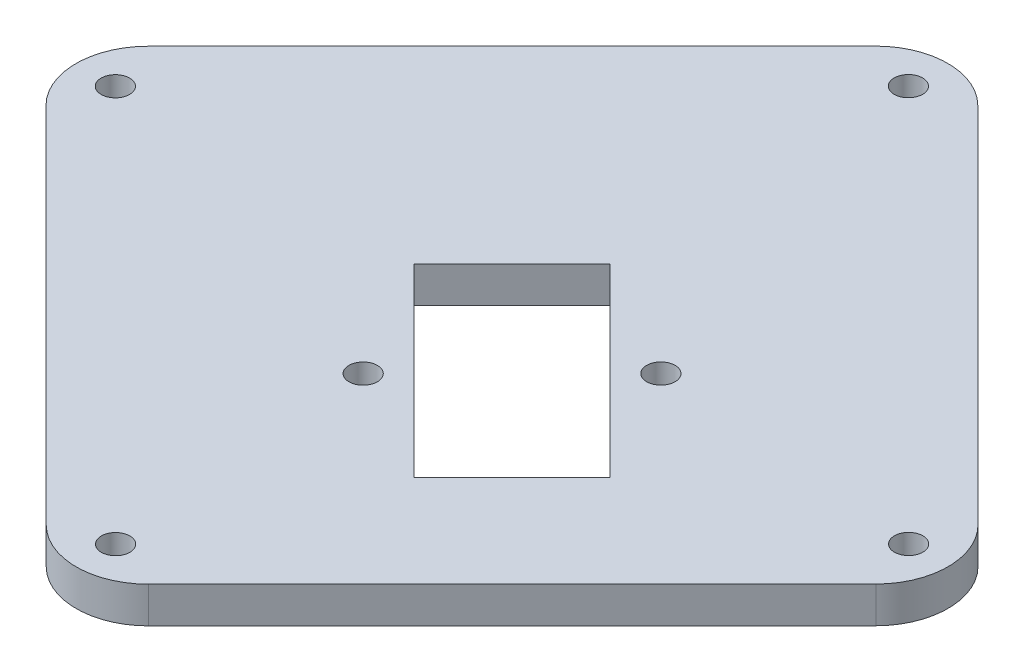
SolidWorks part; units mm, degrees
material "Acrylic (Medium-high impact)"
ref_plane "Front Plane" through (0, 0, 0) normal (0, 0, 1) x (1, 0, 0)
ref_plane "Top Plane" through (0, 0, 0) normal (0, 1, 0) x (1, 0, 0)
ref_plane "Right Plane" through (0, 0, 0) normal (1, 0, 0) x (0, 0, -1)
sketch "Sketch1" plane through (0, 0, 0) normal (0, 1, 0) x (1, 0, 0)
  line L0 (23.2035, -13.3391) -> (6.9491, 2.9051)
  line L1 (6.9491, 2.9051) -> (15.5653, 11.5268)
  line L2 (15.5653, 11.5268) -> (31.8197, -4.7174)
  line L3 (31.8197, -4.7174) -> (23.2035, -13.3391)
  line L4 (15.1477, 44.2388) -> (-25.7632, 3.3021)
  line L5 (-25.7632, 3.3021) -> (15.1735, -37.6088)
  line L7 (15.1735, -37.6088) -> (56.0844, 3.3279)
  line L8 (-5.3078, 23.7705) -> (35.6289, -17.1404) construction
  line L26 (35.616, 23.7834) -> (-5.2949, -17.1533) construction
  line L28 (15.1477, 44.2388) -> (56.0844, 3.3279)
  circle A0 centre (26.142, 5.4116) radius 1.25
  circle A1 centre (13.0709, -7.6678) radius 1.25
  circle A2 centre (-19.6694, 3.304) radius 1.25
  circle A3 centre (15.1496, 38.145) radius 1.25
  circle A4 centre (49.9905, 3.326) radius 1.25
  circle A5 centre (15.1715, -31.5149) radius 1.25
  dimension "D8" = 11.176
  dimension "D9" = 2.5
  dimension "D10" = 18.4912
  dimension "D12" = 4.309
  dimension "D13" = 4.309
  dimension "D14" = 4.309
  dimension "D15" = 4.309
  dimension "D17" = 4.309
  dimension "D18" = 4.309
  dimension "D19" = 4.309
  dimension "D2" = 57.875
  dimension "D3" = 57.875
  dimension "D4" = 12.189
  dimension "D5" = 22.98
  dimension "D6" = 6.0945
  dimension "D7" = 11.476
  dimension "D11" = 9.2456
  dimension "D16" = 4.309
extrude "Boss-Extrude1" add sketch "Sketch1" along normal blind 3.175
fillet "Fillet1" radius 6.35 4 edges at (-25.7632, 1.5875, -3.3021) (15.1477, 1.5875, -44.2388) (15.1735, 1.5875, 37.6088) (56.0844, 1.5875, -3.3279)
